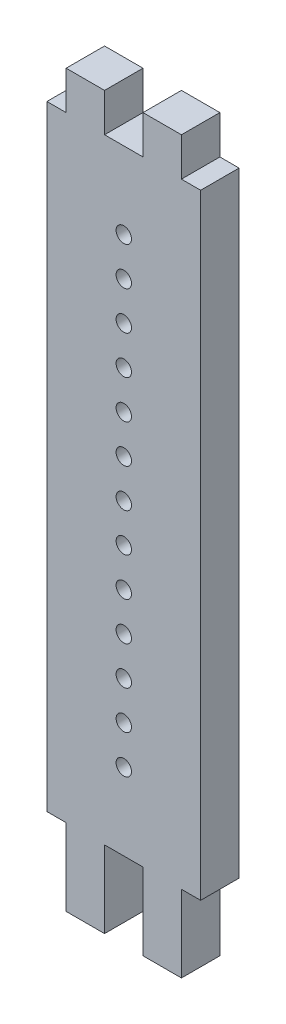
SolidWorks part; units mm, degrees
ref_plane "Front Plane" through (0, 0, 0) normal (0, 0, 1) x (1, 0, 0)
ref_plane "Top Plane" through (0, 0, 0) normal (0, 1, 0) x (1, 0, 0)
ref_plane "Right Plane" through (0, 0, 0) normal (1, 0, 0) x (0, 0, -1)
sketch "Sketch1" plane through (0, 0, 0) normal (0, 0, 1) x (1, 0, 0)
  line L0 (-7.5, 40) -> (-7.5, 45)
  line L1 (-10, -40) -> (-7.5, -40)
  line L2 (-10, -40) -> (-10, 40)
  line L3 (-10, 40) -> (-7.5, 40)
  line L4 (10, -40) -> (10, 40)
  line L5 (-10, -40) -> (10, 40) construction
  line L6 (-10, 40) -> (10, -40) construction
  line L7 (-7.5, 45) -> (-2.5, 45)
  line L8 (-2.5, 45) -> (-2.5, 40)
  line L9 (2.5, 40) -> (2.5, 45)
  line L10 (2.5, 45) -> (7.5, 45)
  line L11 (7.5, 45) -> (7.5, 40)
  line L12 (-2.5, 40) -> (2.5, 40)
  line L13 (7.5, 40) -> (10, 40)
  line L14 (-2.5, -40) -> (2.5, -40)
  line L16 (-7.5, -40) -> (-7.5, -45)
  line L20 (2.5, -40) -> (2.5, -45)
  line L23 (7.5, -40) -> (10, -40)
  line L24 (-7.5, -45) -> (-7.5, -50)
  line L25 (-7.5, -50) -> (-2.5, -50)
  line L26 (-2.5, -50) -> (-2.5, -40)
  line L27 (2.5, -45) -> (2.5, -50)
  line L28 (2.5, -50) -> (7.5, -50)
  line L29 (7.5, -50) -> (7.5, -40)
  line L30 (0, 0) -> (0, 44.2491) construction
  line L31 (0, 0) -> (41.6146, 0) construction
  circle A0 centre (0, 0) radius 1
  circle A1 centre (0, 10) radius 1
  circle A2 centre (0, 20) radius 1
  circle A3 centre (0, 30) radius 1
  circle A4 centre (0, 5) radius 1
  circle A5 centre (0, 15) radius 1
  circle A6 centre (0, 25) radius 1
  circle A7 centre (0, -25) radius 1
  circle A8 centre (0, -15) radius 1
  circle A9 centre (0, -5) radius 1
  circle A10 centre (0, -30) radius 1
  circle A11 centre (0, -20) radius 1
  circle A12 centre (0, -10) radius 1
  point P0 (0, 0)
  dimension "D8" = 2
  dimension "D9" = 10
  dimension "D12" = 10
  dimension "D1" = 5
  dimension "D2" = 5
  dimension "D3" = 20
  dimension "D4" = 5
  dimension "D5" = 80
  dimension "D6" = 5
  dimension "D7" = 10
  dimension "D10" = 10
  dimension "D11" = 10
  dimension "D13" = 10
  dimension "D14" = 5
extrude "Boss-Extrude1" add sketch "Sketch1" along normal blind 5
